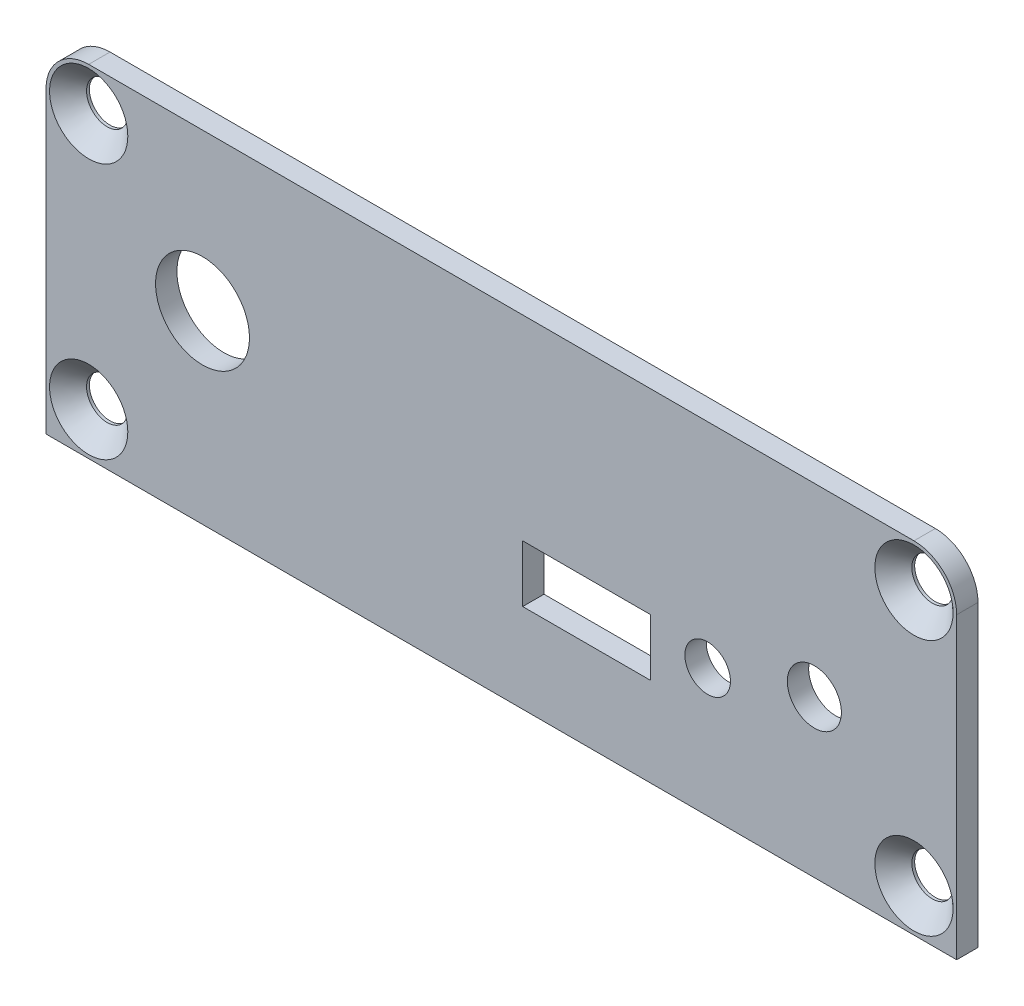
SolidWorks part; units mm, degrees
ref_plane "Front Plane" through (0, 0, 0) normal (0, 0, 1) x (1, 0, 0)
ref_plane "Top Plane" through (0, 0, 0) normal (0, 1, 0) x (1, 0, 0)
ref_plane "Right Plane" through (0, 0, 0) normal (1, 0, 0) x (0, 0, -1)
sketch "Sketch1" plane through (0, 0, 0) normal (0, 0, 1) x (1, 0, 0)
  line L1 (-32, 12) -> (32, 12)
  line L2 (-32, 12) -> (-32, -12)
  line L3 (-32, -12) -> (32, -12)
  line L4 (32, 12) -> (32, -12)
  line L5 (-32, 12) -> (32, -12) construction
  line L6 (-32, -12) -> (32, 12) construction
  point P0 (0, 0)
  dimension "D1" = 64
  dimension "D2" = 24
extrude "Boss-Extrude1" add sketch "Sketch1" against normal blind 1.5
hole_wizard "CSK for M2.5 Flat Head Machine Screw1" positions "Sketch3" profile "Sketch2" countersink size "M2.5" standard "ANSI Metric" end condition through all
sketch "Sketch3" plane through (0, 0, 0) normal (0, 0, 1) x (1, 0, 0)
  line L0 (32, 12) -> (-32, 12) construction
  line L1 (-32, 12) -> (-32, -12) construction
  line L2 (32, -12) -> (32, 12) construction
  line L3 (-32, -12) -> (32, -12) construction
  point P0 (-29, 9)
  point P7 (29, 9)
  point P11 (-29, -9)
  point P15 (29, -9)
  dimension "D1" = 3
  dimension "D2" = 3
  dimension "D3" = 3
  dimension "D4" = 3
sketch "Sketch2" plane through (-29, 9, 0) normal (1, 0, 0) x (0, -1, 0)
  line L0 (0, 0) -> (0, 1.5)
  line L1 (0, 1.5) -> (1.45, 1.5)
  line L2 (1.45, 1.5) -> (1.45, 1.3)
  line L3 (1.45, 1.3) -> (2.75, 0)
  line L5 (2.75, 0) -> (0, 0)
  line L6 (-1.45, 1.3) -> (-2.75, 0) construction
  line L11 (0, -6.35) -> (0, 107.95) construction
  dimension "Thru Hole Dia." = 2.9
  dimension "Thru Hole Depth" = 1.5
  dimension "Near C'Sink Dia." = 5.5
  dimension "Near C'Sink Angle" = 90
fillet "Fillet1" radius 3 2 edges at (-32, 12, -0.75) (32, 12, -0.75)
sketch "Sketch4" plane through (0, 0, 0) normal (0, 0, 1) x (1, 0, 0)
  circle A0 centre (-21, 1) radius 3.3
  dimension "D1" = 1
  dimension "D3" = 6.6
  dimension "D2" = 21
extrude "Cut-Extrude1" cut sketch "Sketch4" against normal through all
sketch "Sketch5" plane through (0, 0, 0) normal (0, 0, 1) x (1, 0, 0)
  circle A0 centre (14.5, -3) radius 1.6
  dimension "D1" = 3
  dimension "D3" = 3.2
  dimension "D2" = 14.5
extrude "Cut-Extrude2" cut sketch "Sketch5" against normal through all
sketch "Sketch6" plane through (0, 0, 0) normal (0, 0, 1) x (1, 0, 0)
  circle A0 centre (22, -1) radius 1.9
  dimension "D1" = 1
  dimension "D3" = 3.8
  dimension "D2" = 22
extrude "Cut-Extrude3" cut sketch "Sketch6" against normal through all
sketch "Sketch7" plane through (0, 0, 0) normal (0, 0, 1) x (1, 0, 0)
  line L1 (1.5, -1.75) -> (10.5, -1.75)
  line L2 (1.5, -1.75) -> (1.5, -5.75)
  line L3 (1.5, -5.75) -> (10.5, -5.75)
  line L4 (10.5, -1.75) -> (10.5, -5.75)
  line L5 (1.5, -1.75) -> (10.5, -5.75) construction
  line L6 (1.5, -5.75) -> (10.5, -1.75) construction
  point P0 (6, -3.75)
  dimension "D1" = 6
  dimension "D2" = 3.75
  dimension "D3" = 4
  dimension "D4" = 9
extrude "Cut-Extrude4" cut sketch "Sketch7" against normal through all
